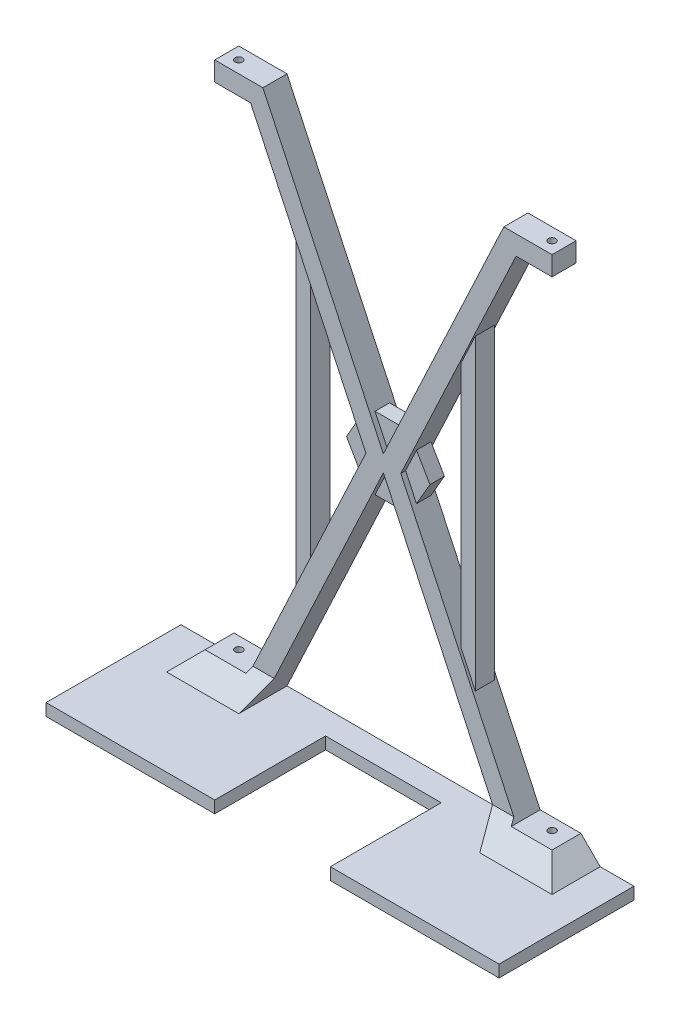
SolidWorks part; units mm, degrees
ref_plane "前视基准面" through (0, 0, 0) normal (0, 0, 1) x (1, 0, 0)
ref_plane "上视基准面" through (0, 0, 0) normal (0, 1, 0) x (1, 0, 0)
ref_plane "右视基准面" through (0, 0, 0) normal (1, 0, 0) x (0, 0, -1)
sketch "草图1" plane through (0, 0, 0) normal (0, 0, 1) x (1, 0, 0)
  line L0 (-70, 106.6029) -> (-50, 106.6029)
  line L1 (-50, 106.6029) -> (0, 0)
  line L2 (-70, 98.6029) -> (-55.084, 98.6029)
  line L3 (-55.084, 98.6029) -> (-7.2429, -3.3971)
  line L4 (-70, 106.6029) -> (-70, 98.6029)
  line L5 (-7.2429, -3.3971) -> (0, 0)
  line L6 (0, -55) -> (0, 55) construction
  line L7 (7.2429, -3.3971) -> (0, 0)
  line L8 (70, 106.6029) -> (70, 98.6029)
  line L9 (55.084, 98.6029) -> (7.2429, -3.3971)
  line L10 (70, 98.6029) -> (55.084, 98.6029)
  line L11 (50, 106.6029) -> (0, 0)
  line L12 (70, 106.6029) -> (50, 106.6029)
  line L13 (-7.2429, -3.3971) -> (7.2429, -3.3971) construction
  line L14 (70, -113.3971) -> (50, -113.3971)
  line L15 (50, -113.3971) -> (0, -6.7943)
  line L16 (70, -105.3971) -> (55.084, -105.3971)
  line L17 (55.084, -105.3971) -> (7.2429, -3.3971)
  line L18 (70, -113.3971) -> (70, -105.3971)
  line L19 (7.2429, -3.3971) -> (0, -6.7943)
  line L20 (-7.2429, -3.3971) -> (0, -6.7943)
  line L21 (-70, -113.3971) -> (-70, -105.3971)
  line L22 (-55.084, -105.3971) -> (-7.2429, -3.3971)
  line L23 (-70, -105.3971) -> (-55.084, -105.3971)
  line L24 (-50, -113.3971) -> (0, -6.7943)
  line L25 (-70, -113.3971) -> (-50, -113.3971)
  dimension "D1" = 8
  dimension "D2" = 100
  dimension "D3" = 20
  dimension "D4" = 220
extrude "凸台-拉伸1" add sketch "草图1" along normal mid plane 10 contours L3 L5 L1 L0 L4 L2 | L8 L12 L11 L7 L9 L10 | L21 L25 L24 L20 L22 L23 | L17 L19 L15 L14 L18 L16 | L5 L13 L7 | L13 L20 L19 region at (-32.4215, 57.3588, 0) region at (0, -2.2648, 0) region at (32.4215, 57.3588, 0) region at (0, -4.5295, 0) region at (-32.4215, -64.1531, 0) region at (32.4215, -64.1531, 0)
sketch "草图2" plane through (0, 106.6029, 0) normal (0, 1, 0) x (1, 0, 0)
  line L0 (0, -55) -> (0, 55) construction
  circle A0 centre (-65, 0) radius 1.55
  circle A1 centre (65, 0) radius 1.55
  dimension "D1" = 3.1
  dimension "D2" = 130
extrude "切除-拉伸1" cut sketch "草图2" against normal blind 234
sketch "草图3" plane through (0, 0, 0) normal (0, 0, 1) x (1, 0, 0)
  line L0 (-7.2429, -3.3971) -> (7.2429, -3.3971) construction
  line L2 (8.6603, 11.6029) -> (-8.6603, 11.6029)
  line L3 (-8.6603, 11.6029) -> (-17.3205, -3.3971)
  line L4 (-17.3205, -3.3971) -> (-8.6603, -18.3971)
  line L5 (-8.6603, -18.3971) -> (8.6603, -18.3971)
  line L6 (8.6603, -18.3971) -> (17.3205, -3.3971)
  line L7 (17.3205, -3.3971) -> (8.6603, 11.6029)
  circle A0 centre (0, -3.3971) radius 15 construction
  dimension "D1" = 30
extrude "凸台-拉伸3" add sketch "草图3" along normal mid plane 6
sketch "草图4" plane through (0, -113.3971, 0) normal (0, -1, 0) x (1, 0, 0)
  line L1 (-94, -5) -> (94, -5)
  line L2 (-94, -5) -> (-94, 5)
  line L3 (-94, 5) -> (94, 5)
  line L4 (94, -5) -> (94, 5)
  line L5 (-94, -5) -> (94, 5) construction
  line L6 (-94, 5) -> (94, -5) construction
  line L7 (-50, 5) -> (0, 5) construction
  line L8 (-50, -5) -> (0, -5) construction
  point P5 (0, 0)
  point P6 (0, -4)
  point P10 (0, -4)
  point P11 (0, 0)
  dimension "D2" = 188
extrude "凸台-拉伸4" add sketch "草图4" along normal blind 5
sketch "草图5" plane through (0, -118.3971, 0) normal (0, -1, 0) x (1, 0, 0)
  line L0 (0, -5.5) -> (0, 5.5) construction
  line L1 (94, 5) -> (24, 5)
  line L2 (94, 5) -> (94, 51)
  line L3 (94, 51) -> (24, 51)
  line L4 (24, 5) -> (24, 51)
  line L5 (-24, 5) -> (-24, 51)
  line L6 (-94, 51) -> (-24, 51)
  line L7 (-94, 5) -> (-94, 51)
  line L8 (-94, 5) -> (-24, 5)
  dimension "D1" = 46
extrude "凸台-拉伸5" add sketch "草图5" against normal blind 5
sketch "草图6" plane through (0, 0, 0) normal (0, 0, 1) x (1, 0, 0)
  line L0 (-31.1634, 47.6029) -> (-31.1634, -54.3971)
  line L1 (-55.084, 98.6029) -> (-7.2429, -3.3971) construction
  line L2 (-55.084, -105.3971) -> (-7.2429, -3.3971) construction
  line L3 (-37.1634, 60.3952) -> (-37.1634, -67.1895)
  line L4 (-31.1634, 47.6029) -> (-37.1634, 60.3952)
  line L5 (-37.1634, -67.1895) -> (-31.1634, -54.3971)
  line L6 (0, -5.5) -> (0, 5.5) construction
  line L7 (37.1634, -67.1895) -> (31.1634, -54.3971)
  line L8 (31.1634, 47.6029) -> (37.1634, 60.3952)
  line L9 (37.1634, 60.3952) -> (37.1634, -67.1895)
  line L10 (31.1634, 47.6029) -> (31.1634, -54.3971)
  dimension "D1" = 6
extrude "凸台-拉伸6" add sketch "草图6" along normal mid plane 8
chamfer "倒角1" distance 10 angle 45 4 edges at (70, -113.3971, 0) (60, -113.3971, 5) (-60, -113.3971, 5) (-70, -113.3971, 0)
